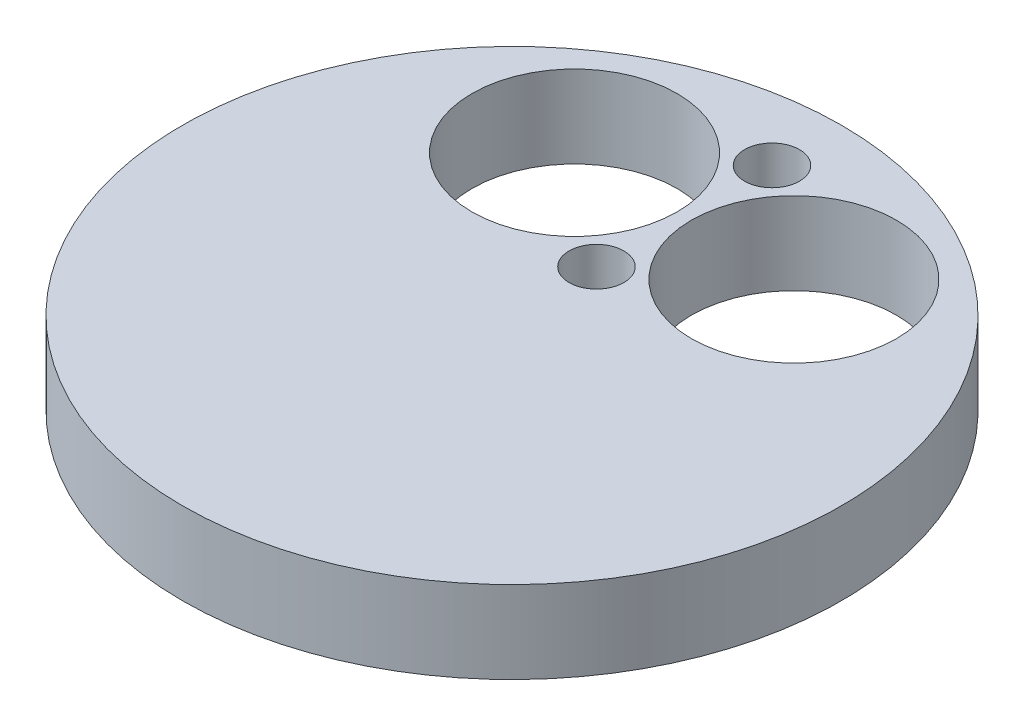
SolidWorks part; units mm, degrees
ref_plane "Front Plane" through (0, 0, 0) normal (0, 0, 1) x (1, 0, 0)
ref_plane "Top Plane" through (0, 0, 0) normal (0, 1, 0) x (1, 0, 0)
ref_plane "Right Plane" through (0, 0, 0) normal (1, 0, 0) x (0, 0, -1)
ref_axis "Axis1" through (0, 55, 0) along (0, -1, 0)
sketch "Sketch1" plane through (0, 0, 0) normal (0, 1, 0) x (1, 0, 0)
  line L0 (-12.7, 19.939) -> (12.7, 19.939) construction
  line L1 (-12.7, 19.939) -> (12.7, 19.939) construction
  line L2 (-12.7, 33.909) -> (12.7, 33.909) construction
  line L3 (-12.7, 5.969) -> (12.7, 5.969) construction
  line L4 (0, 30.099) -> (0, 9.779) construction
  circle A0 centre (0, 0) radius 38.1508
  circle A2 centre (12.7, 19.939) radius 11.8745
  circle A3 centre (-12.7, 19.939) radius 11.8745
  arc A4 (-12.7, 33.909) -> (-12.7, 5.969) centre (-12.7, 19.939) ccw construction
  arc A5 (12.7, 5.969) -> (12.7, 33.909) centre (12.7, 19.939) ccw construction
  circle A6 centre (0, 30.099) radius 3.175
  circle A7 centre (0, 9.779) radius 3.175
  point P4 (0, 19.939)
  point P10 (0, 19.939)
  point P20 (0, 19.939)
  dimension "D1" = 76.3016
  dimension "D2" = 23.749
  dimension "D3" = 23.749
  dimension "D8" = 6.35
  dimension "D9" = 6.35
  dimension "D4" = 25.4
  dimension "D5" = 27.94
  dimension "D6" = 25.4
  dimension "D7" = 19.939
  dimension "D10" = 20.32
extrude "Boss-Extrude1" add sketch "Sketch1" along normal blind 9.525
equation "\"D3@Sketch1\"=\"D2@Sketch1\""
equation "\"D9@Sketch1\"=\"D8@Sketch1\""
